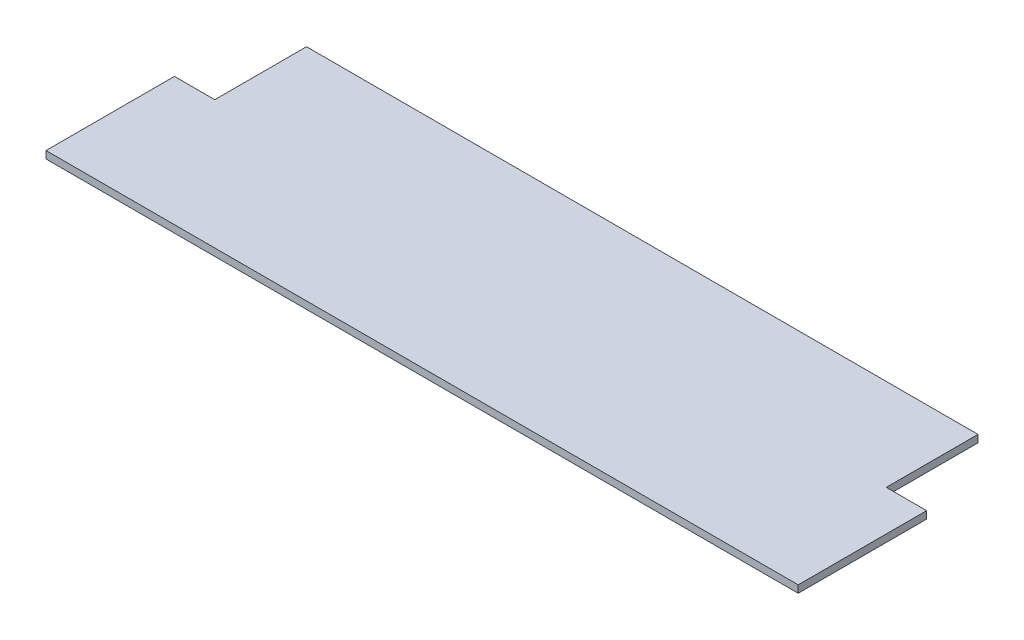
SolidWorks part; units mm, degrees
ref_plane "Front Plane" through (0, 0, 0) normal (0, 0, 1) x (1, 0, 0)
ref_plane "Top Plane" through (0, 0, 0) normal (0, 1, 0) x (1, 0, 0)
ref_plane "Right Plane" through (0, 0, 0) normal (1, 0, 0) x (0, 0, -1)
sketch "Sketch1" plane through (0, 0, 0) normal (0, 1, 0) x (1, 0, 0)
  line L1 (-205, 60) -> (205, 60)
  line L2 (-205, 60) -> (-205, -60)
  line L3 (-205, -60) -> (205, -60)
  line L4 (205, 60) -> (205, -60)
  line L5 (-205, 60) -> (205, -60) construction
  line L6 (-205, -60) -> (205, 60) construction
  point P0 (0, 0)
  dimension "D1" = 120
  dimension "D2" = 410
extrude "Boss-Extrude1" add sketch "Sketch1" along normal blind 4
sketch "Sketch2" plane through (0, 4, 0) normal (0, 1, 0) x (1, 0, 0)
  line L1 (183, 10) -> (233.1702, 10)
  line L2 (183, 10) -> (183, 80.735)
  line L3 (183, 80.735) -> (233.1702, 80.735)
  line L4 (233.1702, 10) -> (233.1702, 80.735)
  line L6 (0, -2.2) -> (0, 2.2) construction
  line L7 (-183, 10) -> (-183, 80.735)
  line L8 (-183, 10) -> (-233.1702, 10)
  line L9 (-233.1702, 10) -> (-233.1702, 80.735)
  line L10 (-183, 80.735) -> (-233.1702, 80.735)
  point P9 (233.1702, 80.735)
extrude "Cut-Extrude1" cut sketch "Sketch2" against normal up to next
